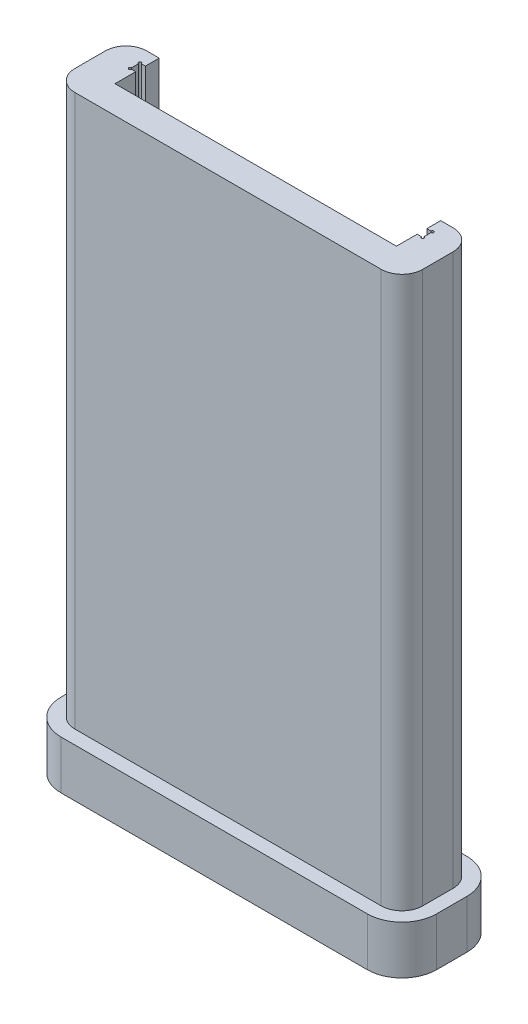
SolidWorks part; units mm, degrees
material "Melamine resin"
ref_plane "Front Plane" through (0, 0, 0) normal (0, 0, 1) x (1, 0, 0)
ref_plane "Top Plane" through (0, 0, 0) normal (0, 1, 0) x (1, 0, 0)
ref_plane "Right Plane" through (0, 0, 0) normal (1, 0, 0) x (0, 0, -1)
sketch "Sketch2" plane through (0, 0, 0) normal (0, 1, 0) x (1, 0, 0)
  line L1 (0, 0) -> (88.9, 0)
  line L2 (0, 0) -> (0, 152.4)
  line L3 (0, 152.4) -> (88.9, 152.4)
  line L10 (88.9, 152.4) -> (88.9, 0)
  dimension "D1" = 152.4
  dimension "D2" = 88.9
extrude "Boss-Extrude1" add sketch "Sketch2" along normal blind 5.9944 contours L3 L10 L1 L2
sketch "Sketch4" plane through (0, 5.9944, 0) normal (0, 1, 0) x (1, 0, 0)
  line L0 (0, 0) -> (0, 152.4) construction
  line L1 (0, 0) -> (88.9, 0) construction
  circle A0 centre (45.72, 109.8713) radius 2.7305
  circle A1 centre (45.72, 33.6713) radius 2.7305
  dimension "D3" = 5.461
  dimension "D4" = 5.461
  dimension "D1" = 76.2
  dimension "D2" = 45.72
  dimension "D5" = 33.6713
extrude "Cut-Extrude2" cut sketch "Sketch4" against normal through all both
sketch "Sketch5" plane through (0, 5.9944, 0) normal (0, 1, 0) x (1, 0, 0)
  line L0 (0, 152.4) -> (88.9, 152.4) construction
  line L1 (12.5095, 15.748) -> (76.3905, 15.748)
  line L2 (12.5095, 15.748) -> (12.5095, 2.54)
  line L3 (12.5095, 2.54) -> (76.3905, 2.54)
  line L4 (76.3905, 15.748) -> (76.3905, 2.54)
  line L5 (18.6055, 7.62) -> (70.2945, 7.62)
  line L6 (18.6055, 7.62) -> (18.6055, 15.748)
  line L7 (18.6055, 15.748) -> (70.2945, 15.748)
  line L8 (70.2945, 7.62) -> (70.2945, 15.748)
  line L9 (17.5895, 13.208) -> (71.3105, 13.208)
  line L10 (17.5895, 13.208) -> (17.5895, 11.43)
  line L11 (17.5895, 11.43) -> (71.3105, 11.43)
  line L12 (71.3105, 13.208) -> (71.3105, 11.43)
  line L13 (0, 0) -> (88.9, 0) construction
  circle A1 centre (17.5895, 13.208) radius 0.254
  circle A2 centre (17.5895, 11.43) radius 0.254
  circle A3 centre (71.3105, 13.208) radius 0.254
  circle A4 centre (71.3105, 11.43) radius 0.254
  point P16 (44.45, 152.4)
  point P17 (44.45, 15.748)
  dimension "D11" = 0.508
  dimension "D12" = 0.508
  dimension "D13" = 0.508
  dimension "D14" = 0.508
  dimension "D1" = 53.721
  dimension "D2" = 6.096
  dimension "D3" = 6.096
  dimension "D4" = 3.81
  dimension "D5" = 2.54
  dimension "D6" = 5.08
  dimension "D7" = 5.08
  dimension "D8" = 1.778
  dimension "D9" = 2.54
  dimension "D10" = 5.08
extrude "Boss-Extrude2" add sketch "Sketch5" along normal blind 101.6 contours L9 L12 L11 L8 L5 L6 L10 L1 L2 L3 L4 region at (44.45, 5.9944, -6.5676)
fillet "Fillet1" radius 3.81 4 edges at (12.5095, 56.7944, -2.54) (12.5095, 56.7944, -15.748) (76.3905, 56.7944, -2.54) (76.3905, 56.7944, -15.748)
sketch "Sketch7" plane through (0, 5.9944, 0) normal (0, 1, 0) x (1, 0, 0)
  line L0 (0, 0) -> (88.9, 0) construction
  line L1 (0, 152.4) -> (2.54, 152.4)
  line L2 (0, 152.4) -> (0, 0)
  line L3 (0, 0) -> (2.54, 0)
  line L4 (2.54, 152.4) -> (2.54, 0)
  dimension "D1" = 2.54
extrude "Cut-Extrude3" cut sketch "Sketch7" against normal through all both
sketch "Sketch11" plane through (0, 0, 0) normal (0, -1, 0) x (1, 0, 0)
  line L4 (2.54, 0) -> (2.54, -152.4)
  line L5 (2.54, -152.4) -> (88.9, -152.4)
  line L6 (88.9, -152.4) -> (88.9, 0)
  line L7 (88.9, 0) -> (2.54, 0)
  line L8 (2.54, 0) -> (2.54, -152.4)
  line L9 (2.54, -152.4) -> (88.9, -152.4)
  line L10 (88.9, -152.4) -> (88.9, 0)
  line L11 (88.9, 0) -> (2.54, 0)
  dimension "D1" = 0
extrude "Cut-Extrude4" cut sketch "Sketch11" against normal blind 6.35
sketch "Sketch12" plane through (0, 6.35, 0) normal (0, -1, 0) x (1, 0, 0)
  line L0 (18.6055, -15.748) -> (70.2945, -15.748)
  line L1 (70.2945, -18.288) -> (72.5805, -18.288)
  line L2 (78.9305, -11.938) -> (78.9305, -6.35)
  line L3 (72.5805, 0) -> (16.3195, 0)
  line L4 (9.9695, -6.35) -> (9.9695, -11.938)
  line L5 (16.3195, -18.288) -> (18.6055, -18.288)
  line L6 (18.6055, -18.288) -> (70.2945, -18.288)
  line L16 (71.3105, -11.684) -> (71.3105, -12.954)
  line L17 (71.0565, -13.208) -> (70.2945, -13.208)
  line L18 (70.2945, -13.208) -> (70.2945, -15.748)
  line L19 (70.2945, -15.748) -> (72.5805, -15.748)
  line L20 (76.3905, -11.938) -> (76.3905, -6.35)
  line L21 (72.5805, -2.54) -> (16.3195, -2.54)
  line L22 (12.5095, -6.35) -> (12.5095, -11.938)
  line L23 (16.3195, -15.748) -> (18.6055, -15.748)
  line L24 (18.6055, -15.748) -> (18.6055, -13.208)
  line L25 (18.6055, -13.208) -> (17.8435, -13.208)
  line L26 (17.5895, -12.954) -> (17.5895, -11.684)
  line L27 (17.8435, -11.43) -> (18.6055, -11.43)
  line L28 (18.6055, -11.43) -> (18.6055, -7.62)
  line L29 (18.6055, -7.62) -> (70.2945, -7.62)
  line L30 (70.2945, -7.62) -> (70.2945, -11.43)
  line L31 (70.2945, -11.43) -> (71.0565, -11.43)
  line L32 (71.3105, -11.684) -> (71.3105, -12.954)
  line L33 (71.0565, -13.208) -> (70.2945, -13.208)
  line L34 (70.2945, -13.208) -> (70.2945, -15.748)
  line L35 (70.2945, -15.748) -> (72.5805, -15.748)
  line L36 (76.3905, -11.938) -> (76.3905, -6.35)
  line L37 (72.5805, -2.54) -> (16.3195, -2.54)
  line L38 (12.5095, -6.35) -> (12.5095, -11.938)
  line L39 (16.3195, -15.748) -> (18.6055, -15.748)
  line L40 (18.6055, -15.748) -> (18.6055, -13.208)
  line L41 (18.6055, -13.208) -> (17.8435, -13.208)
  line L42 (17.5895, -12.954) -> (17.5895, -11.684)
  line L43 (17.8435, -11.43) -> (18.6055, -11.43)
  line L44 (18.6055, -11.43) -> (18.6055, -7.62)
  line L45 (18.6055, -7.62) -> (70.2945, -7.62)
  line L46 (70.2945, -7.62) -> (70.2945, -11.43)
  line L47 (70.2945, -11.43) -> (71.0565, -11.43)
  arc A0 (72.5805, -18.288) -> (78.9305, -11.938) centre (72.5805, -11.938) ccw
  arc A1 (78.9305, -6.35) -> (72.5805, 0) centre (72.5805, -6.35) ccw
  arc A2 (16.3195, 0) -> (9.9695, -6.35) centre (16.3195, -6.35) ccw
  arc A3 (9.9695, -11.938) -> (16.3195, -18.288) centre (16.3195, -11.938) ccw
  arc A4 (72.5805, -15.748) -> (76.3905, -11.938) centre (72.5805, -11.938) ccw
  arc A5 (76.3905, -6.35) -> (72.5805, -2.54) centre (72.5805, -6.35) ccw
  arc A6 (16.3195, -2.54) -> (12.5095, -6.35) centre (16.3195, -6.35) ccw
  arc A7 (12.5095, -11.938) -> (16.3195, -15.748) centre (16.3195, -11.938) ccw
  arc A8 (72.5805, -15.748) -> (76.3905, -11.938) centre (72.5805, -11.938) ccw
  arc A9 (76.3905, -6.35) -> (72.5805, -2.54) centre (72.5805, -6.35) ccw
  arc A10 (16.3195, -2.54) -> (12.5095, -6.35) centre (16.3195, -6.35) ccw
  arc A11 (12.5095, -11.938) -> (16.3195, -15.748) centre (16.3195, -11.938) ccw
  arc A17 (17.5895, -12.954) -> (17.8435, -13.208) centre (17.5895, -13.208) ccw
  arc A18 (17.5895, -12.954) -> (17.8435, -13.208) centre (17.5895, -13.208) ccw
  arc A22 (71.0565, -13.208) -> (71.3105, -12.954) centre (71.3105, -13.208) ccw
  arc A23 (71.0565, -13.208) -> (71.3105, -12.954) centre (71.3105, -13.208) ccw
  arc A24 (17.8435, -11.43) -> (17.5895, -11.684) centre (17.5895, -11.43) ccw
  arc A25 (17.8435, -11.43) -> (17.5895, -11.684) centre (17.5895, -11.43) ccw
  arc A26 (71.3105, -11.684) -> (71.0565, -11.43) centre (71.3105, -11.43) ccw
  arc A27 (71.3105, -11.684) -> (71.0565, -11.43) centre (71.3105, -11.43) ccw
  line M22 (71.3105, -11.684) -> (71.3105, -12.954)
  line M23 (71.0565, -13.208) -> (70.2945, -13.208)
  line M24 (70.2945, -13.208) -> (70.2945, -15.748)
  line M25 (70.2945, -15.748) -> (72.5805, -15.748)
  arc M26 (72.5805, -15.748) -> (76.3905, -11.938) centre (72.5805, -11.938) ccw
  line M27 (76.3905, -11.938) -> (76.3905, -6.35)
  arc M28 (76.3905, -6.35) -> (72.5805, -2.54) centre (72.5805, -6.35) ccw
  line M29 (72.5805, -2.54) -> (16.3195, -2.54)
  arc M30 (16.3195, -2.54) -> (12.5095, -6.35) centre (16.3195, -6.35) ccw
  line M31 (12.5095, -6.35) -> (12.5095, -11.938)
  arc M32 (12.5095, -11.938) -> (16.3195, -15.748) centre (16.3195, -11.938) ccw
  line M33 (16.3195, -15.748) -> (18.6055, -15.748)
  line M34 (18.6055, -15.748) -> (18.6055, -13.208)
  line M35 (18.6055, -13.208) -> (17.8435, -13.208)
  line M36 (17.5895, -12.954) -> (17.5895, -11.684)
  line M37 (17.8435, -11.43) -> (18.6055, -11.43)
  line M38 (18.6055, -11.43) -> (18.6055, -7.62)
  line M39 (18.6055, -7.62) -> (70.2945, -7.62)
  line M40 (70.2945, -7.62) -> (70.2945, -11.43)
  line M41 (70.2945, -11.43) -> (71.0565, -11.43)
  dimension "D1" = 0
  dimension "D2" = 2.54
extrude "Boss-Extrude3" add sketch "Sketch12" along normal blind 8.89 contours L4 A3 L5 L6 L1 A0 L2 A1 L3 A2 L0 M33 M32 M31 M30 M29 M28 M27 M26 M25 | M41 M22 M23 M24 M25 M26 M27 M28 M29 M30 M31 M32 M33 M34 M35 M36 M37 M38 M39 M40 | L0 M34 M24 M23 M22 M41 M40 M39 M38 M37 M36 M35 region at (44.45, 6.35, -11.6903) region at (44.45, 6.35, -6.4887) region at (44.45, 6.35, -17.5746)
sketch "Sketch13" plane through (0, -2.54, 0) normal (0, -1, 0) x (1, 0, 0)
  line L0 (19.05, -9.144) -> (69.85, -9.144) construction
  line L1 (72.5805, 0) -> (16.3195, 0) construction
  line L2 (78.9305, -11.938) -> (78.9305, -6.35) construction
  circle A0 centre (19.05, -9.144) radius 2.7305
  circle A1 centre (69.85, -9.144) radius 2.7305
  point P6 (44.45, 0)
  point P7 (44.45, -9.144)
  point P10 (78.9305, -9.144)
  dimension "D1" = 5.461
  dimension "D2" = 5.461
  dimension "D3" = 50.8
extrude "Cut-Extrude5" cut sketch "Sketch13" against normal blind 6.35
equation "\"threaded_insert_hole\"=0.1472"
equation "\"th\"=1.25249"
